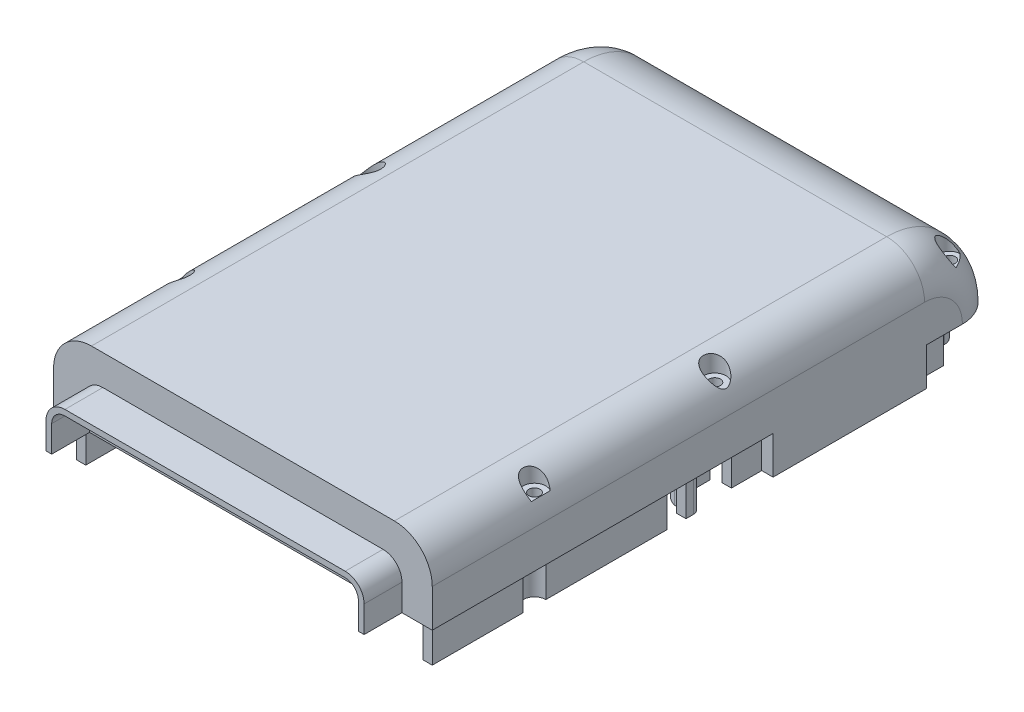
SolidWorks part; units mm, degrees
ref_plane "Front" through (0, 0, 0) normal (0, 0, 1) x (1, 0, 0)
ref_plane "Top" through (0, 0, 0) normal (0, 1, 0) x (1, 0, 0)
ref_plane "Right" through (0, 0, 0) normal (1, 0, 0) x (0, 0, -1)
sketch "草图1" plane through (0, 0, 0) normal (0, 1, 0) x (1, 0, 0)
  line L5 (50, 75) -> (-50, 75)
  line L6 (50, 75) -> (50, -75)
  line L7 (50, -75) -> (-50, -75)
  line L8 (-50, 75) -> (-50, -75)
  line L9 (50, 75) -> (-50, -75) construction
  line L10 (50, -75) -> (-50, 75) construction
  point P0 (0, 0)
  dimension "D1" = 100
  dimension "D2" = 150
extrude "凸台-拉伸1" add sketch "草图1" along normal blind 20
fillet "圆角1" radius 10 4 edges at (-50, 20, 0) (-50, 10, -75) (50, 10, -75) (50, 20, 0)
fillet "圆角2" radius 20 3 edges at (-47.0711, 17.0711, -72.0711) (47.0711, 17.0711, -72.0711) (0, 20, -75)
shell "抽壳6" thickness 3
sketch "草图5" plane through (0, 0, 0) normal (0, -1, 0) x (1, 0, 0)
  line L0 (47, 72) -> (47, -65) construction
  line L1 (50, -55.5) -> (47, -55.5)
  line L2 (50, -55.5) -> (50, -15)
  line L3 (50, -15) -> (47, -15)
  line L4 (47, -55.5) -> (47, -15)
  line L11 (0, 0) -> (0, -53.9289) construction
  line L12 (-47, -55.5) -> (-47, -15)
  line L13 (-50, -15) -> (-47, -15)
  line L14 (-50, -55.5) -> (-50, -15)
  line L15 (-50, -55.5) -> (-47, -55.5)
  dimension "D1" = 40.5
extrude "凸台-拉伸2" add sketch "草图5" along normal blind 10
sketch "草图6" plane through (0, 0, 0) normal (0, -1, 0) x (1, 0, 0)
  line L0 (47, 72) -> (47, -15) construction
  line L1 (44.5, -63) -> (47, -63)
  line L2 (44.5, -63) -> (44.5, -7)
  line L3 (44.5, -7) -> (47, -7)
  line L4 (47, -63) -> (47, -7)
  line L5 (44.3, -7) -> (47, -7) construction
  line L7 (-44.5, -7) -> (-47, -7)
  line L8 (-44.5, -7) -> (-44.5, -63)
  line L9 (-44.5, -63) -> (-47, -63)
  line L10 (-47, -7) -> (-47, -63)
  line L11 (-44.3, -63) -> (-47, -63) construction
  dimension "D1" = 2.5
  dimension "D2" = 2.5
extrude "凸台-拉伸3" add sketch "草图6" along normal blind 10 and the other way up to next
sketch "草图7" plane through (0, 0, 0) normal (0, -1, 0) x (1, 0, 0)
  line L8 (0, 0) -> (0, -100.1928) construction
  line L16 (-38.3, -69.5) -> (38.3, -69.5)
  line L17 (-38.8, -63.5) -> (-41.3, -63.5)
  line L27 (-31.6, -61) -> (-31.6, -58.5)
  line L30 (-38.8, -69) -> (-38.8, -63.5)
  line L31 (-31.6, -61) -> (-11.1, -61)
  line L32 (-11.1, -61) -> (-11.1, -9.5)
  line L36 (-31.6, -9.5) -> (-31.6, -12)
  line L37 (-11.1, -9.5) -> (-31.6, -9.5)
  line L42 (-47, -7) -> (-47, 72) construction
  line L46 (-31.6, -12) -> (-13.6, -12)
  line L47 (-13.6, -12) -> (-13.6, -58.5)
  line L48 (-13.6, -58.5) -> (-31.6, -58.5)
  line L49 (-41.3, -63.5) -> (-41.3, -69)
  line L67 (-47, 10.0516) -> (-44.5, 10)
  line L68 (-44.5, 10) -> (-44.5, 40.101)
  line L69 (-47, 10.0516) -> (-47, 39.5)
  line L70 (-47, 50.5) -> (-47, 72)
  line L71 (-47, 72) -> (47, 72) construction
  line L72 (-47, 72) -> (-44.5, 72)
  line L73 (-44.5, 72) -> (-44.5, 49.899)
  line L74 (-47, 50.5) -> (-47, 48)
  line L75 (-47, 42) -> (-47, 39.5)
  line L76 (47, 42) -> (47, 39.5)
  line L77 (47, 50.5) -> (47, 48)
  line L78 (44.5, 69) -> (44.5, 49.899)
  line L79 (47, 72) -> (44.5, 72)
  line L80 (47, 50.5) -> (47, 72)
  line L81 (47, 10.0516) -> (47, 39.5)
  line L82 (44.5, 10) -> (44.5, 40.101)
  line L83 (47, 10.0516) -> (44.5, 10)
  line L84 (41.3, -63.5) -> (41.3, -69)
  line L85 (13.6, -58.5) -> (31.6, -58.5)
  line L86 (13.6, -12) -> (13.6, -58.5)
  line L87 (31.6, -12) -> (13.6, -12)
  line L95 (11.1, -9.5) -> (31.6, -9.5)
  line L96 (31.6, -9.5) -> (31.6, -12)
  line L97 (11.1, -61) -> (11.1, -9.5)
  line L98 (31.6, -61) -> (11.1, -61)
  line L99 (38.8, -69) -> (38.8, -63.5)
  line L101 (31.6, -61) -> (31.6, -58.5)
  line L102 (38.8, -63.5) -> (41.3, -63.5)
  line L111 (44.5, 69) -> (44.5, 72)
  line L112 (38.3, -72) -> (-38.3, -72)
  line L117 (47, 3) -> (47, 5)
  line L118 (41.3, -1) -> (41.3, -7)
  line L119 (41.3, -7) -> (38.8, -7)
  line L120 (38.8, -7) -> (38.8, -1)
  line L121 (43.3, 1) -> (45, 1)
  line L122 (47, 5) -> (44.4486, 5)
  line L123 (-47, 5) -> (-44.4486, 5)
  line L124 (-43.3, 1) -> (-45, 1)
  line L125 (-38.8, -7) -> (-38.8, -1)
  line L126 (-41.3, -7) -> (-38.8, -7)
  line L127 (-41.3, -1) -> (-41.3, -7)
  line L128 (-47, 3) -> (-47, 5)
  arc A0 (-47, 42) -> (-47, 48) centre (-47, 45) ccw
  arc A15 (-38.8, -69) -> (-38.3, -69.5) centre (-38.3, -69) ccw
  arc A18 (-44.5, 40.101) -> (-44.5, 49.899) centre (-47, 45) ccw
  arc A19 (44.5, 40.101) -> (44.5, 49.899) centre (47, 45) cw
  arc A22 (38.8, -69) -> (38.3, -69.5) centre (38.3, -69) cw
  arc A27 (47, 42) -> (47, 48) centre (47, 45) cw
  arc A33 (-41.3, -69) -> (-38.3, -72) centre (-38.3, -69) ccw
  arc A34 (38.3, -72) -> (41.3, -69) centre (38.3, -69) ccw
  arc A35 (45, 1) -> (47, 3) centre (45, 3) ccw
  arc A36 (43.3, 1) -> (41.3, -1) centre (43.3, -1) ccw
  arc A37 (43.0619, 3.4937) -> (38.8, -1) centre (43.3, -1) ccw
  arc A38 (42.4332, 3.4157) -> (44.4855, 5) centre (42.5, 5.4506) ccw
  arc A39 (-42.4332, 3.4157) -> (-44.4855, 5) centre (-42.5, 5.4506) cw
  arc A40 (-43.0619, 3.4937) -> (-38.8, -1) centre (-43.3, -1) cw
  arc A41 (-43.3, 1) -> (-41.3, -1) centre (-43.3, -1) cw
  arc A42 (-45, 1) -> (-47, 3) centre (-45, 3) cw
  point P26 (0, -72)
  point P36 (0, -69.5)
  point P55 (0, -69.5)
  line M5 (-47, -7) -> (-47, 72)
  line M6 (-47, 72) -> (47, 72)
  line M7 (47, 72) -> (47, -7)
extrude "凸台-拉伸4" add sketch "草图7" along normal blind 11 and the other way up to next contours L68 A18 L73 A0 L67 M6 M5 | A27 L111 L78 A19 L82 L83 M7 M6 | A38 A37 L120 L119 L118 A36 L121 A35 L122 M7 | A42 L124 A41 L127 L126 L125 A40 A39 L123 M5 | L47 L48 L27 L31 L32 L37 L36 L46 | L98 L101 L85 L86 L87 L96 L95 L97 | L16 L8 L112 A34 L84 L102 L99 A22 | L8 L16 A15 L30 L17 L49 A33 L112
sketch "草图23" plane through (0, 0, 0) normal (0, -1, 0) x (-1, 0, 0)
  line L1 (-47, -48) -> (-47, -42) construction
  circle A0 centre (47, -45) radius 3
  circle A1 centre (-47, -45) radius 3
extrude "凸台-拉伸13" add sketch "草图23" against normal up to body
sketch "草图9" plane through (0, 0, 0) normal (0, -1, 0) x (-1, 0, 0)
  line L4 (-47, -3) -> (-47, 7) construction
  line L5 (-47, -3) -> (-47, 7)
  line L6 (-42.8, 15) -> (-44.5, 15)
  line L7 (-44.5, 7) -> (-44.5, 63) construction
  line L8 (-44.5, 15) -> (-44.5, 7)
  line L9 (-44.5, 7) -> (-47, 7)
  line L11 (-40.8, 13) -> (-40.8, 1)
  line L12 (-42.8, -1) -> (-45, -1)
  line L13 (-45, -1) -> (-43.3, -1) construction
  line L14 (0, 0) -> (0, 18.6927)
  line L15 (42.8, -1) -> (45, -1)
  line L16 (40.8, 13) -> (40.8, 1)
  line L17 (44.5, 7) -> (47, 7)
  line L18 (44.5, 15) -> (44.5, 7)
  line L19 (42.8, 15) -> (44.5, 15)
  line L20 (47, -3) -> (47, 7)
  circle A0 centre (-47, -45) radius 3
  circle A1 centre (47, -45) radius 3
  arc A2 (-45, -1) -> (-47, -3) centre (-45, -3) ccw
  arc A3 (-40.8, 1) -> (-42.8, -1) centre (-42.8, 1) cw
  arc A4 (40.8, 1) -> (42.8, -1) centre (42.8, 1) ccw
  arc A5 (45, -1) -> (47, -3) centre (45, -3) cw
  arc A6 (-42.8, 15) -> (-40.8, 13) centre (-42.8, 13) cw
  arc A7 (42.8, 15) -> (40.8, 13) centre (42.8, 13) ccw
  point P46 (-40.8, 15)
  point P49 (40.8, 15)
  dimension "D1" = 2
  dimension "D2" = 2
  dimension "D3" = 2
extrude "凸台-拉伸5" add sketch "草图9" against normal up to body
sketch "草图10" plane through (0, 0, 0) normal (0, -1, 0) x (1, 0, 0)
  line L3 (-40, -72) -> (-40, -62)
  line L4 (-42, -60) -> (-44.5, -60)
  line L7 (-44.5, -60) -> (-44.5, -63)
  line L10 (-44.5, -63) -> (-47, -63)
  line L11 (-47, -63) -> (-47, -65)
  line L12 (0, 0) -> (0, -94.4608) construction
  line L13 (47, -63) -> (47, -65)
  line L14 (44.5, -63) -> (47, -63)
  line L15 (44.5, -60) -> (44.5, -63)
  line L16 (42, -60) -> (44.5, -60)
  line L17 (40, -72) -> (40, -62)
  line L18 (-47, -65) -> (-47, -72)
  line L19 (-47, -72) -> (-40, -72)
  line L20 (40, -72) -> (47, -72)
  line L21 (47, -72) -> (47, -65)
  arc A2 (-40, -62) -> (-42, -60) centre (-42, -62) ccw
  arc A6 (40, -62) -> (42, -60) centre (42, -62) cw
  point P27 (-40, -60)
  point P36 (40, -60)
  dimension "D1" = 2
extrude "凸台-拉伸6" add sketch "草图10" against normal up to body
sketch "草图11" plane through (0, 0, 0) normal (0, -1, 0) x (1, 0, 0)
  circle A0 centre (-45.65, -66) radius 1.5
  circle A1 centre (-45.6051, -4) radius 1.5
  circle A2 centre (-47, 45) radius 1.4854
  circle A3 centre (47, 45) radius 1.5
  circle A4 centre (45.6051, -4) radius 1.5
  circle A5 centre (45.65, -66) radius 1.5
extrude "切除-拉伸1" cut sketch "草图11" against normal through all and the other way blind 10
sketch "草图13" plane through (0, 0, 75) normal (0, 0, 1) x (1, 0, 0)
  line L0 (-50, 0) -> (50, 0) construction
  line L5 (-42, 0) -> (42, 0)
  line L6 (-42, 0) -> (-42, 7)
  line L7 (-37, 12) -> (37, 12)
  line L16 (42, 0) -> (42, 7)
  line L18 (50, 10) -> (50, 0) construction
  line L19 (-50, 10) -> (-50, 0) construction
  arc A4 (42, 7) -> (37, 12) centre (37, 7) ccw
  arc A5 (-37, 12) -> (-42, 7) centre (-37, 7) ccw
  dimension "D4" = 5
  dimension "D2" = 8
  dimension "D3" = 8
sketch "草图14" plane through (0, 0, 75) normal (0, 0, 1) x (1, 0, 0)
  line L22 (-42, 0) -> (-42, 7)
  line L23 (-37, 12) -> (37, 12)
  line L24 (42, 0) -> (42, 7)
  line L25 (-50, 0) -> (50, 0) construction
  line L28 (40.5, 1.5) -> (40.5, 7)
  line L29 (-37, 10.5) -> (37, 10.5)
  line L30 (-40.5, 1.5) -> (-40.5, 7)
  line L34 (-42, 0) -> (42, 0) construction
  line L35 (-40.5, 1.5) -> (40.5, 1.5) construction
  line L46 (-42, 0) -> (-40.5, 0)
  line L47 (-42, 0) -> (-40, 0) construction
  line L48 (-40.5, 0) -> (-40.5, 1.5)
  line L50 (40.5, 1.5) -> (40.5, 0)
  line L52 (40, 0) -> (42, 0) construction
  line L53 (40.5, 0) -> (42, 0)
  arc A4 (37, 12) -> (42, 7) centre (37, 7) cw
  arc A5 (-37, 12) -> (-42, 7) centre (-37, 7) ccw
  arc A6 (37, 10.5) -> (40.5, 7) centre (37, 7) cw
  arc A7 (-37, 10.5) -> (-40.5, 7) centre (-37, 7) ccw
  dimension "D2" = 1.5
  dimension "D1" = 5
extrude "凸台-拉伸7" add sketch "草图14" along normal blind 10
sketch "草图15" plane through (0, 20, 0) normal (0, 1, 0) x (1, 0, 0)
  circle A2 centre (45.6051, 4) radius 3
  circle A5 centre (-45.6051, 4) radius 3
  circle A7 centre (-47, -45) radius 3
  circle A8 centre (47, -45) radius 3
  dimension "D1" = 6
extrude "切除-拉伸4" cut sketch "草图15" against normal blind 5
sketch "草图16" plane through (0, 20, 0) normal (0, 1, 0) x (1, 0, 0)
  circle A0 centre (-45.65, 66) radius 2.8
  circle A1 centre (45.65, 66) radius 2.8
  dimension "D1" = 5.6
extrude "切除-拉伸5" cut sketch "草图16" against normal blind 8
ref_plane "基准面1" through (0, -9, 0) normal (0, -1, 0) x (-1, 0, 0)
sketch "草图22" plane through (0, -9, 0) normal (0, -1, 0) x (-1, 0, 0)
  line L0 (0, 0) -> (0, 84.2923) construction
  line L1 (44.5, 15) -> (41.3, 15)
  line L2 (44.5, 15) -> (44.5, 55.4694)
  line L3 (44.5, 55.4694) -> (41.3, 55.4694)
  line L5 (41.3, 58.5) -> (13.6, 58.5)
  line L6 (41.3, 58.5) -> (41.3, 55.4694)
  line L7 (41.3, 12) -> (13.6, 12)
  line L8 (13.6, 58.5) -> (13.6, 12)
  line L17 (41.3, 15) -> (41.3, 12)
  line L18 (-41.3, 15) -> (-41.3, 12)
  line L19 (-13.6, 58.5) -> (-13.6, 12)
  line L20 (-41.3, 12) -> (-13.6, 12)
  line L21 (-41.3, 58.5) -> (-41.3, 55.4694)
  line L22 (-41.3, 58.5) -> (-13.6, 58.5)
  line L23 (-44.5, 55.4694) -> (-41.3, 55.4694)
  line L24 (-44.5, 15) -> (-44.5, 55.4694)
  line L25 (-44.5, 15) -> (-41.3, 15)
  line L26 (44.5, 63) -> (44.5, 7) construction
  line L27 (-44.5, 7) -> (-44.5, 63) construction
extrude "凸台-拉伸11" add sketch "草图22" against normal blind 3
sketch "草图19" plane through (0, -9, 0) normal (0, -1, 0) x (1, 0, 0)
  line L6 (-21.4, -55.5) -> (-31.4, -55.5)
  line L7 (-21.4, -55.5) -> (-21.4, -58.5)
  line L8 (-21.4, -58.5) -> (-31.4, -58.5)
  line L9 (-31.4, -55.5) -> (-31.4, -58.5)
  line L13 (-13.6, -58.5) -> (-31.6, -58.5) construction
  line L14 (13.6, -58.5) -> (31.6, -58.5) construction
  line L15 (21.5, -55.5) -> (31.5, -55.5)
  line L16 (21.5, -55.5) -> (21.5, -58.5)
  line L17 (21.5, -58.5) -> (31.5, -58.5)
  line L18 (31.5, -55.5) -> (31.5, -58.5)
extrude "凸台-拉伸9" add sketch "草图19" along normal blind 12
sketch "草图20" plane through (0, 0, -55.5) normal (0, 0, 1) x (1, 0, 0)
  line L6 (21.5, -19.2) -> (21.5, -21)
  line L7 (21.5, -21) -> (31.5, -21)
  line L8 (31.5, -21) -> (31.5, -19.2)
  line L10 (-31.4, -20.8) -> (-31.4, -21.6775)
  line L11 (-31.4, -21.6775) -> (-21.404, -21.6775)
  line L12 (-21.404, -21.6775) -> (-21.4, -20.8)
  arc A3 (31.5, -19.2) -> (21.5, -19.2) centre (26.5, -19.2) ccw
  arc A4 (-21.4002, -20.8456) -> (-31.4, -20.8) centre (-26.4, -20.8) ccw
extrude "切除-拉伸6" cut sketch "草图20" against normal up to next
sketch "草图21" plane through (0, 0, -61) normal (0, 0, -1) x (-1, 0, 0)
  line L0 (42, 0) -> (-42, 0) construction
  line L1 (-27.25, 0) -> (-25.75, 0)
  line L2 (-27.25, 0) -> (-27.25, -16.9865)
  line L3 (-27.25, -16.9865) -> (-25.75, -16.9865)
  line L4 (-25.75, 0) -> (-25.75, -16.9865)
  line L5 (25.75, -18.55) -> (27.25, -18.55)
  line L6 (25.75, -18.55) -> (25.75, 0)
  line L7 (25.75, 0) -> (27.25, 0)
  line L8 (27.25, -18.55) -> (27.25, 0)
extrude "凸台-拉伸10" add sketch "草图21" along normal blind 1.5
sketch "草图25" plane through (0, 17, 0) normal (0, -1, 0) x (1, 0, 0)
  circle A0 centre (0, 55) radius 9.6
  circle A1 centre (0, 55) radius 12.6
  dimension "D1" = 3
extrude "凸台-拉伸14" add sketch "草图25" along normal blind 10
sketch "草图26" plane through (0, -11, 0) normal (0, -1, 0) x (1, 0, 0)
  line L0 (-13.6, -12) -> (-13.6, -58.5) construction
  line L1 (-13.6, -58.5) -> (-21.4, -58.5) construction
  line L2 (-21.4, -58.5) -> (-31.4, -58.5) construction
  line L3 (-31.4, -58.5) -> (-31.6, -58.5) construction
  line L4 (-31.6, -58.5) -> (-31.6, -61) construction
  line L5 (-31.6, -61) -> (-27.25, -61) construction
  line L6 (-27.25, -61) -> (-25.75, -61) construction
  line L7 (-25.75, -61) -> (-11.1, -61) construction
  line L8 (-11.1, -61) -> (-11.1, -9.5) construction
  line L9 (-11.1, -9.5) -> (-31.6, -9.5) construction
  line L10 (-31.6, -9.5) -> (-31.6, -12) construction
  line L11 (-31.6, -12) -> (-13.6, -12) construction
  line L12 (27.25, -61) -> (31.6, -61) construction
  line L13 (31.6, -61) -> (31.6, -58.5) construction
  line L14 (31.6, -58.5) -> (31.5, -58.5) construction
  line L15 (31.5, -58.5) -> (21.5, -58.5) construction
  line L16 (21.5, -58.5) -> (13.6, -58.5) construction
  line L17 (13.6, -58.5) -> (13.6, -12) construction
  line L18 (13.6, -12) -> (31.6, -12) construction
  line L19 (31.6, -12) -> (31.6, -9.5) construction
  line L20 (31.6, -9.5) -> (11.1, -9.5) construction
  line L21 (11.1, -9.5) -> (11.1, -61) construction
  line L22 (11.1, -61) -> (25.75, -61) construction
  line L23 (25.75, -61) -> (27.25, -61) construction
  line L24 (27.25, -61) -> (31.6, -61)
  line L25 (31.6, -61) -> (31.6, -58.5)
  line L26 (31.6, -58.5) -> (31.5, -58.5)
  line L27 (31.5, -58.5) -> (21.5, -58.5)
  line L28 (21.5, -58.5) -> (13.6, -58.5)
  line L29 (13.6, -58.5) -> (13.6, -12)
  line L30 (13.6, -12) -> (31.6, -12)
  line L31 (31.6, -12) -> (31.6, -9.5)
  line L32 (31.6, -9.5) -> (11.1, -9.5)
  line L33 (11.1, -9.5) -> (11.1, -61)
  line L34 (11.1, -61) -> (25.75, -61)
  line L35 (25.75, -61) -> (27.25, -61)
  line L36 (-13.6, -12) -> (-13.6, -58.5)
  line L37 (-13.6, -58.5) -> (-21.4, -58.5)
  line L38 (-21.4, -58.5) -> (-31.4, -58.5)
  line L39 (-31.4, -58.5) -> (-31.6, -58.5)
  line L40 (-31.6, -58.5) -> (-31.6, -61)
  line L41 (-31.6, -61) -> (-27.25, -61)
  line L42 (-27.25, -61) -> (-25.75, -61)
  line L43 (-25.75, -61) -> (-11.1, -61)
  line L44 (-11.1, -61) -> (-11.1, -9.5)
  line L45 (-11.1, -9.5) -> (-31.6, -9.5)
  line L46 (-31.6, -9.5) -> (-31.6, -12)
  line L47 (-31.6, -12) -> (-13.6, -12)
extrude "切除-拉伸8" cut sketch "草图26" against normal blind 1
